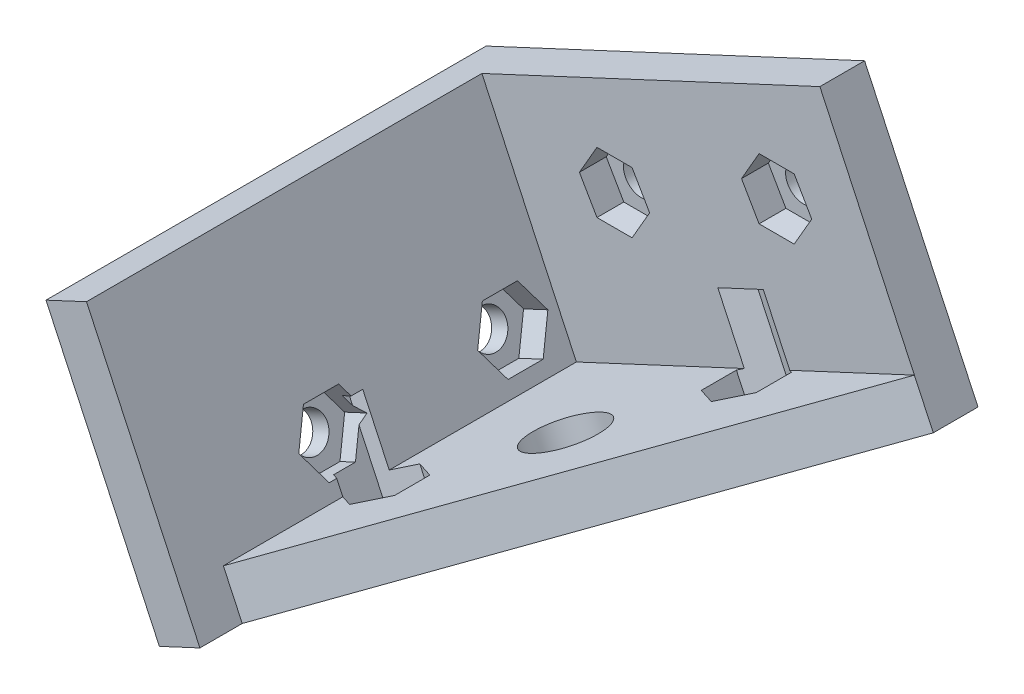
SolidWorks part; units mm, degrees
material "ABS"
ref_plane "Front Plane" through (0, 0, 0) normal (0, 0, 1) x (1, 0, 0)
ref_plane "Top Plane" through (0, 0, 0) normal (0, 1, 0) x (1, 0, 0)
ref_plane "Right Plane" through (0, 0, 0) normal (1, 0, 0) x (0, 0, -1)
sketch "Sketch1" plane through (0, 0, 0) normal (0, 0, 1) x (1, 0, 0)
  line L0 (-27.1677, -320.4736) -> (-39.8463, -293.2844)
  line L1 (-90.5605, -184.5274) -> (-27.1677, -320.4736) construction
  line L2 (-39.8463, -293.2844) -> (2.4783, -273.5481)
  line L3 (2.4783, -273.5481) -> (15.1568, -300.7373)
  line L4 (332.3646, -152.8209) -> (-30.1585, -321.8683) construction
  line L5 (15.1568, -300.7373) -> (-27.1677, -320.4736)
  line L7 (-6.2846, -286.8374) -> (-4.3216, -290.2374)
  line L8 (-4.3216, -290.2374) -> (-0.3956, -290.2374)
  line L9 (-0.3956, -290.2374) -> (1.5674, -286.8374)
  line L10 (1.5674, -286.8374) -> (-0.3956, -283.4374)
  line L11 (-0.3956, -283.4374) -> (-4.3216, -283.4374)
  line L12 (-4.3216, -283.4374) -> (-6.2846, -286.8374)
  line L13 (-24.4107, -295.2897) -> (-22.4477, -298.6897)
  line L14 (-22.4477, -298.6897) -> (-18.5218, -298.6897)
  line L15 (-18.5218, -298.6897) -> (-16.5588, -295.2897)
  line L16 (-16.5588, -295.2897) -> (-18.5218, -291.8897)
  line L17 (-18.5218, -291.8897) -> (-22.4477, -291.8897)
  line L18 (-22.4477, -291.8897) -> (-24.4107, -295.2897)
  circle A0 centre (-2.3586, -286.8374) radius 2 construction
  circle A1 centre (-2.3586, -286.8374) radius 2
  circle A2 centre (-20.4847, -295.2897) radius 2
  circle A3 centre (-20.4847, -295.2897) radius 2 construction
  circle A4 centre (-2.3586, -286.8374) radius 3.4 construction
  circle A5 centre (-20.4847, -295.2897) radius 3.4 construction
  dimension "D1" = 10
  dimension "D2" = 10
  dimension "D3" = 6.8
  dimension "D4" = 6.8
extrude "Boss-Extrude1" add sketch "Sketch1" along normal blind 2 contours L5 L3 L2 L0 L18 L17 L16 L15 L14 L13 L12 L11 L10 L9 L8 L7 | L11 L12 L7 L8 L9 L10 A1 | L17 L18 L13 L14 L15 L16 A2 region at (-12.4007, -297.3715, 0) region at (-5.2131, -285.1893, 0) region at (-23.3393, -293.6417, 0)
extrude "Boss-Extrude2" add sketch "Sketch1<3>" along normal blind 3 from surface contours L5 L3 L2 L0 L18 L17 L16 L15 L14 L13 L12 L11 L10 L9 L8 L7 region at (-12.4007, -297.3715, 0) starting at face at (-12.3447, -297.0109, 2)
sketch "Sketch1<3>" plane through (0, 0, 0) normal (0, 0, 1) x (1, 0, 0) same geometry as "Sketch1"
sketch "Sketch3" plane through (117.8962, -252.8292, 0) normal (-0.4226, 0.9063, 0) x (0.9063, 0.4226, 0)
  line L0 (-113.3603, 0) -> (-113.3603, -5)
  line L1 (-113.3603, -5) -> (-160.0603, -49.2058)
  line L2 (-160.0603, 0) -> (-160.0603, -393.4) construction
  line L3 (-160.0603, -49.2058) -> (-160.0603, -5)
  line L5 (-149.3537, -26.5568) -> (-152.7537, -24.5938)
  line L6 (-152.7537, -24.5938) -> (-156.1537, -26.5568)
  line L7 (-156.1537, -26.5568) -> (-156.1537, -30.4828)
  line L8 (-156.1537, -30.4828) -> (-152.7537, -32.4458)
  line L9 (-152.7537, -32.4458) -> (-149.3537, -30.4828)
  line L10 (-149.3537, -30.4828) -> (-149.3537, -26.5568)
  line L11 (-131.5405, -3.3806) -> (-134.9405, -5.3436)
  line L12 (-134.9405, -5.3436) -> (-134.9405, -9.2696)
  line L13 (-134.9405, -9.2696) -> (-131.5405, -11.2326)
  line L14 (-131.5405, -11.2326) -> (-128.1405, -9.2696)
  line L15 (-128.1405, -9.2696) -> (-128.1405, -5.3436)
  line L16 (-128.1405, -5.3436) -> (-131.5405, -3.3806)
  line L17 (-113.3603, 0) -> (-160.0603, 0)
  line L18 (-160.0603, 0) -> (-160.0603, -5)
  circle A0 centre (-152.7537, -28.5198) radius 2 construction
  circle A1 centre (-131.5405, -7.3066) radius 2
  circle A2 centre (-152.7537, -28.5198) radius 2
  circle A3 centre (-152.7537, -28.5198) radius 3.4 construction
  circle A4 centre (-131.5405, -7.3066) radius 3.4 construction
  dimension "D1" = 10
  dimension "D2" = 4
  dimension "D3" = 4
  dimension "D4" = 6.8
  dimension "D5" = 6.8
extrude "Boss-Extrude3" add sketch "Sketch3" along normal blind 2 contours L17 L18 L3 L1 L0 L10 L9 L8 L7 L6 L5 L16 L15 L14 L13 L12 L11 | L15 L16 L11 L12 L13 L14 | L9 L10 L5 L6 L7 L8 region at (-11.8139, -313.314, 16.464) region at (-17.5584, -315.9927, 28.5198) region at (0.1737, -307.7241, 4.4521)
extrude "Boss-Extrude4" add sketch "Sketch3<4>" along normal blind 3 from surface contours L17 L18 L3 L1 L0 L10 L9 L8 L7 L6 L5 L16 L15 L14 L13 L12 L11 region at (-11.8139, -313.314, 16.464) starting at face at (-13.9048, -312.0822, 19.7353)
sketch "Sketch3<4>" plane through (117.8962, -252.8292, 0) normal (-0.4226, 0.9063, 0) x (0.9063, 0.4226, 0) same geometry as "Sketch3"
sketch "Sketch4" plane through (-145.0639, -67.6444, 0) normal (0.9063, 0.4226, 0) x (0, 0, -1)
  line L0 (-49.2058, -278.9662) -> (-49.2058, -248.9662)
  line L1 (-49.2058, -248.9662) -> (-5, -248.9662)
  line L2 (-5, -248.9662) -> (-5, -278.9662)
  line L3 (-5, -278.9662) -> (-49.2058, -278.9662)
  line L4 (-5, -248.9662) -> (0, -248.9662) construction
  line L6 (-33.926, -268.9662) -> (-31.963, -272.3662)
  line L7 (-31.963, -272.3662) -> (-28.037, -272.3662)
  line L8 (-28.037, -272.3662) -> (-26.074, -268.9662)
  line L9 (-26.074, -268.9662) -> (-28.037, -265.5662)
  line L10 (-28.037, -265.5662) -> (-31.963, -265.5662)
  line L11 (-31.963, -265.5662) -> (-33.926, -268.9662)
  line L12 (-13.926, -268.9662) -> (-11.963, -272.3662)
  line L13 (-11.963, -272.3662) -> (-8.037, -272.3662)
  line L14 (-8.037, -272.3662) -> (-6.074, -268.9662)
  line L15 (-6.074, -268.9662) -> (-8.037, -265.5662)
  line L16 (-8.037, -265.5662) -> (-11.963, -265.5662)
  line L17 (-11.963, -265.5662) -> (-13.926, -268.9662)
  circle A0 centre (-10, -268.9662) radius 2
  circle A1 centre (-30, -268.9662) radius 2
  circle A2 centre (-30, -268.9662) radius 3.4 construction
  circle A3 centre (-10, -268.9662) radius 3.4 construction
  point P14 (-27.0555, -267.2662)
  circle M11 centre (-30, -268.9662) radius 2
  circle M12 centre (-10, -268.9662) radius 2
  line M18 (-393.4, -278.9662) -> (0, -278.9662)
  dimension "D3" = 4
  dimension "D4" = 4
  dimension "D1" = 6.8
  dimension "D2" = 6.8
extrude "Boss-Extrude5" add sketch "Sketch4" along normal blind 2 contours L2 L1 L0 L17 L16 L15 L14 L13 L12 L11 L10 L9 L8 L7 L6 M18 | L10 L11 L6 L7 L8 L9 M11 | L16 L17 L12 L13 L14 L15 M12 region at (-33.6428, -306.5877, 27.5594) region at (-32.0904, -309.9169, 32.8545) region at (-32.0904, -309.9169, 12.8545)
extrude "Boss-Extrude6" add sketch "Sketch4<4>" along normal blind 3 from surface contours L2 L1 L0 L17 L16 L15 L14 L13 L12 L11 L10 L9 L8 L7 L6 M18 region at (-33.6428, -306.5877, 27.5594) starting at face at (-30.2857, -309.0548, 33.8395)
sketch "Sketch4<4>" plane through (-145.0639, -67.6444, 0) normal (0.9063, 0.4226, 0) x (0, 0, -1) same geometry as "Sketch4"
extrude "Cut-Extrude1" cut sketch "Sketch3<5>" along normal blind 10 from surface contours L15 L16 L11 L12 L13 L14 | L9 L10 L5 L6 L7 L8 region at (-17.5584, -315.9927, 28.5198) region at (0.1737, -307.7241, 4.4521) starting at face at (-3.9779, -307.4532, 7.3066)
sketch "Sketch3<5>" plane through (117.8962, -252.8292, 0) normal (-0.4226, 0.9063, 0) x (0.9063, 0.4226, 0) same geometry as "Sketch3"
sketch "Sketch5" plane through (117.8962, -252.8292, 0) normal (0.4226, -0.9063, 0) x (0.9063, 0.4226, 0)
  line L0 (-131.5405, 7.3066) -> (-152.7537, 28.5198) construction
  circle A0 centre (-142.1471, 17.9132) radius 4
  dimension "D1" = 8
extrude "Cut-Extrude2" cut sketch "Sketch5" against normal blind 10
